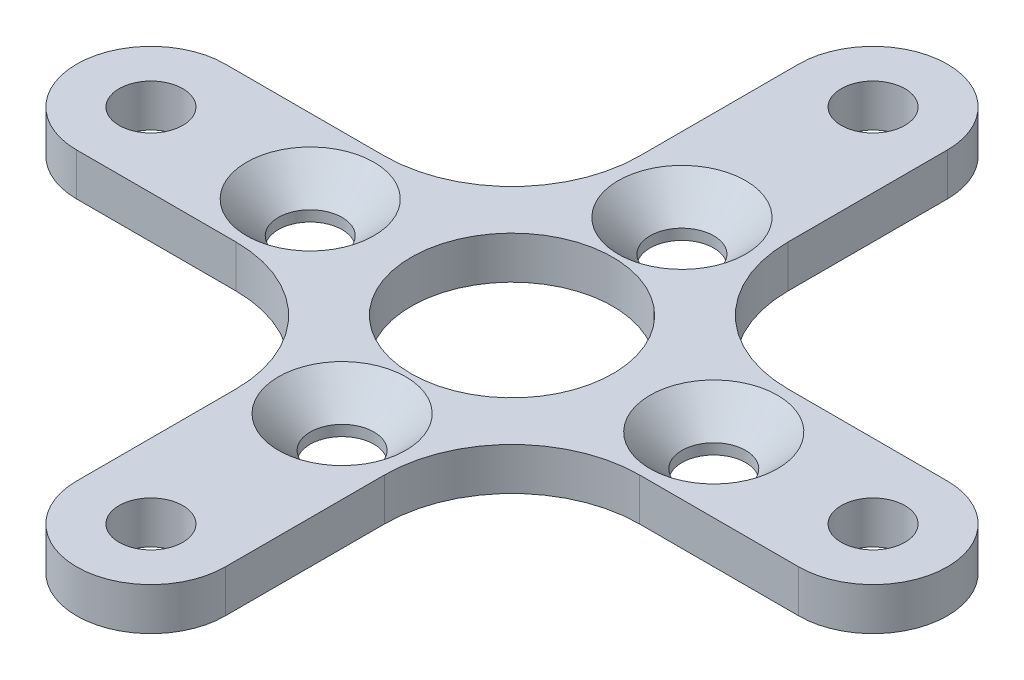
SolidWorks part; units mm, degrees
material "6061-T6 (SS)"
ref_plane "Front Plane" through (0, 0, 0) normal (0, 0, 1) x (1, 0, 0)
ref_plane "Top Plane" through (0, 0, 0) normal (0, 1, 0) x (1, 0, 0)
ref_plane "Right Plane" through (0, 0, 0) normal (1, 0, 0) x (0, 0, -1)
ref_axis "X" through (-88.99, 0, 0) along (1, 0, 0)
ref_axis "Y" through (0, 55, 0) along (0, -1, 0)
ref_axis "Z" through (0, 0, -88.99) along (0, 0, 1)
sketch "Sketch1" plane through (0, 0, 0) normal (0, 1, 0) x (1, 0, 0)
  line L0 (-9.5, 0) -> (9.5, 0) construction
  line L1 (9.5, 0) -> (17, 0) construction
  line L2 (-9.5, 0) -> (-17, 0) construction
  line L3 (0, -8) -> (0, 8) construction
  line L4 (0, 8) -> (0, -17) construction
  line L5 (0, -8) -> (0, 17) construction
  line L6 (3.5, 17) -> (3.5, 9.5)
  line L7 (17, 3.5) -> (9.5, 3.5)
  line L8 (17, -3.5) -> (9.5, -3.5)
  line L9 (3.5, -9.5) -> (3.5, -17)
  line L10 (-3.5, -17) -> (-3.5, -9.5)
  line L11 (-9.5, -3.5) -> (-17, -3.5)
  line L12 (-17, 3.5) -> (-9.5, 3.5)
  line L13 (-3.5, 9.5) -> (-3.5, 17)
  circle A0 centre (0, 0) radius 4.75
  arc A1 (17, 3.5) -> (17, -3.5) centre (17, 0) cw
  arc A2 (3.5, -17) -> (-3.5, -17) centre (0, -17) cw
  arc A3 (-17, -3.5) -> (-17, 3.5) centre (-17, 0) cw
  arc A4 (-3.5, 17) -> (3.5, 17) centre (0, 17) cw
  circle A5 centre (0, 8) radius 1.5
  circle A6 centre (0, 17) radius 1.5
  circle A7 centre (17, 0) radius 1.5
  circle A8 centre (9.5, 0) radius 1.5
  circle A9 centre (0, -17) radius 1.5
  circle A10 centre (0, -8) radius 1.5
  circle A11 centre (-17, 0) radius 1.5
  circle A12 centre (-9.5, 0) radius 1.5
  circle A13 centre (0, 0) radius 17 construction
  arc A14 (9.5, 3.5) -> (3.5, 9.5) centre (9.5, 9.5) cw
  arc A15 (9.5, -3.5) -> (3.5, -9.5) centre (9.5, -9.5) ccw
  arc A16 (-3.5, -9.5) -> (-9.5, -3.5) centre (-9.5, -9.5) ccw
  arc A17 (-9.5, 3.5) -> (-3.5, 9.5) centre (-9.5, 9.5) ccw
  point P6 (0, 0)
  point P10 (0, 0)
  point P13 (0, 0)
  point P18 (-20.5, 0)
  point P47 (20.5, 0)
  dimension "D1" = 9.5
  dimension "D4" = 3
  dimension "D5" = 41
  dimension "D6" = 34
  dimension "D2" = 19
  dimension "D3" = 16
  dimension "D7" = 7
extrude "Boss-Extrude1" add sketch "Sketch1" along normal blind 2
chamfer "Chamfer1" distance 1.5 angle 45 4 edges at (-9.5, 2, 1.5) (0, 2, 9.5) (9.5, 2, 1.5) (0, 2, -6.5)
